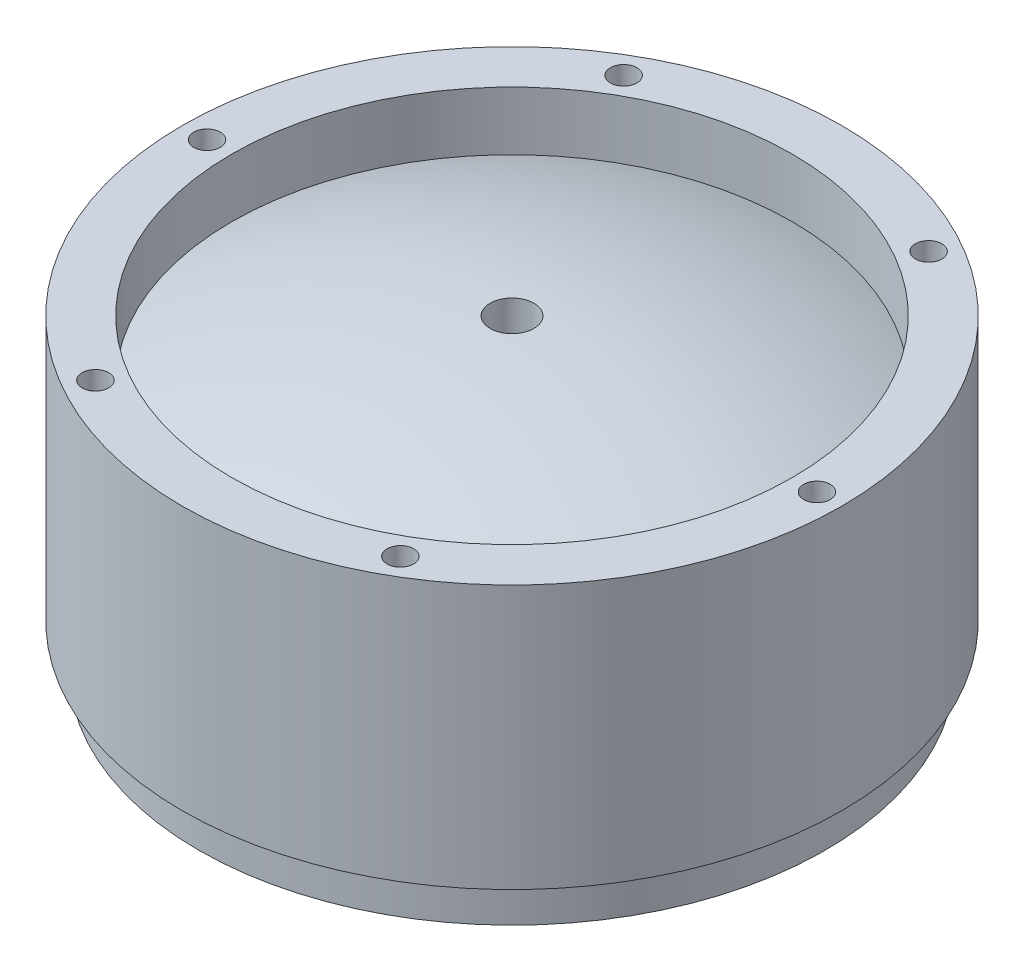
SolidWorks part; units mm, degrees
material "6061-T6 (SS)"
ref_plane "Front Plane" through (0, 0, 0) normal (0, 0, 1) x (1, 0, 0)
ref_plane "Top Plane" through (0, 0, 0) normal (0, 1, 0) x (1, 0, 0)
ref_plane "Right Plane" through (0, 0, 0) normal (1, 0, 0) x (0, 0, -1)
ref_axis "Axis1" through (0, 127.061, 0) along (0, -1, 0)
sketch "Sketch1" plane through (0, 0, 0) normal (0, 0, 1) x (1, 0, 0)
  line L0 (-63.5, 8.1831) -> (-63.5, 58.9831)
  line L1 (-60.325, 6.35) -> (-63.5, 8.1831)
  line L2 (0, 127.061) -> (0, -81.9141) construction
  line L4 (-60.325, 6.35) -> (-60.325, 0)
  line L5 (-60.325, 0) -> (-57.9437, 0)
  line L6 (55, 0) -> (-55, 0) construction
  line L7 (-63.5, 58.9831) -> (-53.975, 58.9831)
  line L8 (-63.5, 8.1831) -> (-60.325, 6.35)
  line L9 (-53.975, 58.9831) -> (-53.975, 47.6967)
  line L10 (-4.2164, 58.9831) -> (-4.2164, 51.9944)
  line L15 (-57.9437, 0) -> (-57.9437, 6.35)
  line L16 (-57.9437, 6.35) -> (-54.2846, 27.1023)
  arc A0 (-54.2846, 27.1023) -> (-41.4524, 45.109) centre (-35.2346, 27.1023) cw
  arc A1 (-41.4524, 45.109) -> (-4.2164, 51.9944) centre (0, -74.9356) cw
  arc A3 (-53.975, 47.6967) -> (-4.2164, 58.9831) centre (0, -74.9356) cw
  point P14 (-59.1344, 0)
  point P15 (0, 0)
  point P17 (0, 0)
  dimension "D5" = 19.05
  dimension "D6" = 127
  dimension "D7" = 133.985
  dimension "D8" = 50.8
  dimension "D2" = 170
  dimension "D3" = 6.35
  dimension "D4" = 2.3813
  dimension "D9" = 3.175
  dimension "D10" = 9.525
  dimension "D13" = 4.2164
  dimension "D16" = 63.5
  dimension "D17" = 120
revolve "Revolve2" add sketch "Sketch1" angle 360 about axis through (0, 127.061, 0) along (0, -1, 0) region at (-62.6637, 33.5831, 0)
sketch "Sketch2" plane through (0, 0, 0) normal (0, 0, 1) x (1, 0, 0)
  line L0 (0, 127.061) -> (0, -81.9141) construction
  line L1 (0, 87.1374) -> (-97.8719, 87.1374)
  line L2 (0, 87.1374) -> (0, -26.2798)
  line L3 (0, -26.2798) -> (-97.8719, -26.2798)
  line L4 (-97.8719, 87.1374) -> (-97.8719, -26.2798)
revolve "Cut-Revolve1" [suppressed] cut sketch "Sketch2" angle 315 about axis through (0, 127.061, 0) along (0, -1, 0)
ref_plane "Plane2" through (0, 6.35, 0) normal (0, -1, 0) x (-1, 0, 0)
sketch "Sketch8" plane through (0, 0, 0) normal (0, 0, 1) x (1, 0, 0)
  line L0 (0, 127.061) -> (0, -81.9141) construction
  line L1 (0, 89.8009) -> (92.4947, 89.8009)
  line L2 (0, 89.8009) -> (0, -18.1338)
  line L3 (0, -18.1338) -> (92.4947, -18.1338)
  line L4 (92.4947, 89.8009) -> (92.4947, -18.1338)
revolve "Cut-Revolve2" [suppressed] cut sketch "Sketch8" angle 300 about axis through (0, 127.061, 0) along (0, -1, 0) other way angle 30 reverse direction yes
hole_wizard "1/4-20 Tapped Hole1" positions "Sketch9" profile "Sketch11" tap size "1/4-20" standard "ANSI Inch"
sketch "Sketch9" plane through (0, 58.9831, 0) normal (0, 1, 0) x (1, 0, 0)
  line L0 (-55, 0) -> (55, 0) construction
  circle A1 centre (0, 0) radius 63.5 construction
  point P0 (-58.7375, 0)
  point P3 (0, 0)
  point P8 (0, 0)
  dimension "D1" = 58.7375
sketch "Sketch11" plane through (-58.7375, 58.9831, 0) normal (1, 0, 0) x (0, 0, 1)
  line L0 (0, 0) -> (0, 14.2338)
  line L1 (0, 14.2338) -> (2.5527, 12.7)
  line L2 (2.5527, 12.7) -> (2.5527, 0)
  line L5 (2.5527, 0) -> (0, 0)
  line L10 (0, 14.2338) -> (-2.5527, 12.7) construction
  line L11 (0, -6.35) -> (0, 107.95) construction
  dimension "Tap Drill Dia." = 5.1054
  dimension "Tap Drill Depth" = 12.7
  dimension "Drill Angle" = 118
cosmetic thread "Hole Thread1" parameters "D1"=9.525, "D2"=6.35
pattern_circular "CirPattern1" count 6 over 360 about axis through (0, 127.061, 0) along (0, -1, 0) of "1/4-20 Tapped Hole1"
